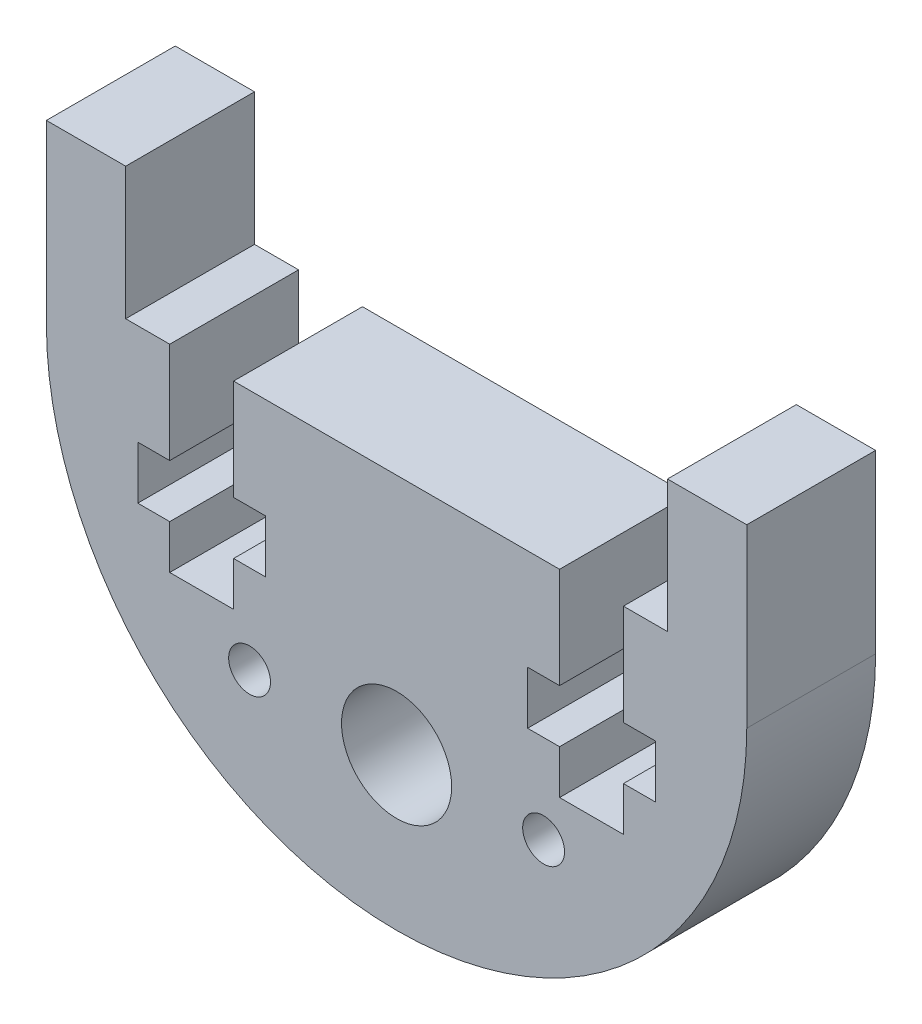
SolidWorks part; units mm, degrees
material "Acrylic (Medium-high impact)"
ref_plane "Front Plane" through (0, 0, 0) normal (0, 0, 1) x (1, 0, 0)
ref_plane "Top Plane" through (0, 0, 0) normal (0, 1, 0) x (1, 0, 0)
ref_plane "Right Plane" through (0, 0, 0) normal (1, 0, 0) x (0, 0, -1)
sketch "Model" plane through (0, 0, 0) normal (0, 0, 1) x (1, 0, 0)
  line L0 (546.1095, 558.5325) -> (553.5095, 558.5325)
  line L1 (553.5095, 547.5325) -> (553.5095, 540.8575) construction
  line L2 (553.5095, 547.5325) -> (553.5095, 540.8575) construction
  line L3 (546.8345, 547.5325) -> (553.5095, 547.5325) construction
  line L4 (560.1845, 547.5325) -> (553.5095, 547.5325) construction
  line L5 (553.5095, -443.4675) -> (553.5095, 49556.5325) construction
  line L6 (553.5095, 547.5325) -> (553.5095, 540.8575) construction
  line L7 (553.5095, 540.8575) -> (553.5095, 547.5325) construction
  line L8 (560.9095, 553.9566) -> (560.9095, 558.5325)
  line L9 (559.4595, 553.9566) -> (560.9095, 553.9566)
  line L10 (559.4595, 551.5565) -> (559.4595, 553.9566)
  line L11 (560.9095, 551.5565) -> (559.4595, 551.5565)
  line L12 (560.9095, 549.5565) -> (560.9095, 551.5565)
  line L13 (563.8095, 549.5565) -> (560.9095, 549.5565)
  line L14 (563.8095, 551.5565) -> (563.8095, 549.5565)
  line L15 (565.2595, 551.5565) -> (563.8095, 551.5565)
  line L16 (565.2595, 553.9566) -> (565.2595, 551.5565)
  line L17 (563.8095, 553.9566) -> (565.2595, 553.9566)
  line L18 (563.8095, 558.5325) -> (563.8095, 553.9566)
  line L19 (565.8095, 558.5325) -> (563.8095, 558.5325)
  line L20 (565.8095, 564.5325) -> (565.8095, 558.5325)
  line L21 (569.4095, 564.5325) -> (565.8095, 564.5325)
  line L22 (569.4095, 556.5325) -> (569.4095, 564.5325)
  line L23 (560.9095, 558.5325) -> (553.5095, 558.5325)
  line L24 (553.5095, 547.5325) -> (553.5095, 553.0893) construction
  line L25 (543.2095, 558.5325) -> (546.1095, 558.5325) construction
  line L26 (544.6595, 558.5325) -> (544.6595, 549.5565) construction
  line L27 (562.3595, 558.5325) -> (562.3595, 549.5565) construction
  line L28 (560.9095, 558.5325) -> (563.8095, 558.5325) construction
  line L41 (537.6095, 556.5325) -> (537.6095, 564.5325)
  line L42 (537.6095, 564.5325) -> (541.2095, 564.5325)
  line L43 (541.2095, 564.5325) -> (541.2095, 558.5325)
  line L44 (541.2095, 558.5325) -> (543.2095, 558.5325)
  line L45 (543.2095, 558.5325) -> (543.2095, 553.9566)
  line L46 (543.2095, 553.9566) -> (541.7595, 553.9566)
  line L47 (541.7595, 553.9566) -> (541.7595, 551.5565)
  line L48 (541.7595, 551.5565) -> (543.2095, 551.5565)
  line L49 (543.2095, 551.5565) -> (543.2095, 549.5565)
  line L50 (543.2095, 549.5565) -> (546.1095, 549.5565)
  line L51 (546.1095, 549.5565) -> (546.1095, 551.5565)
  line L52 (546.1095, 551.5565) -> (547.5595, 551.5565)
  line L53 (547.5595, 551.5565) -> (547.5595, 553.9566)
  line L54 (547.5595, 553.9566) -> (546.1095, 553.9566)
  line L55 (546.1095, 553.9566) -> (546.1095, 558.5325)
  circle A0 centre (546.8345, 547.5325) radius 0.95
  circle A1 centre (553.5095, 547.5325) radius 2.5
  arc A4 (569.4095, 556.5325) -> (537.6095, 556.5325) centre (553.5095, 556.5325) cw
  circle A8 centre (560.1845, 547.5325) radius 0.95
  point P7 (544.6595, 558.5325)
  dimension "D10" = 6.675
  dimension "D9" = 1.9
  dimension "D14" = 5
  dimension "D1" = 3.6
  dimension "D2" = 6
  dimension "D3" = 8
  dimension "D4" = 2.4001
  dimension "D5" = 1.45
  dimension "D6" = 4.5759
  dimension "D7" = 2
  dimension "D8" = 2
  dimension "D11" = 7.4
  dimension "D12" = 11
  dimension "D13" = 2.9
extrude "Boss-Extrude2" add sketch "Model" along normal blind 5.85 contours A4 L22 L21 L20 L19 L18 L17 L16 L15 L14 L13 L12 L11 L10 L9 L8 L23 L0 L55 L54 L53 L52 L51 L50 L49 L48 L47 L46 L45 L44 L43 L42 L41 A1 A0 A8 region at (553.5095, 551.7089, 0)
